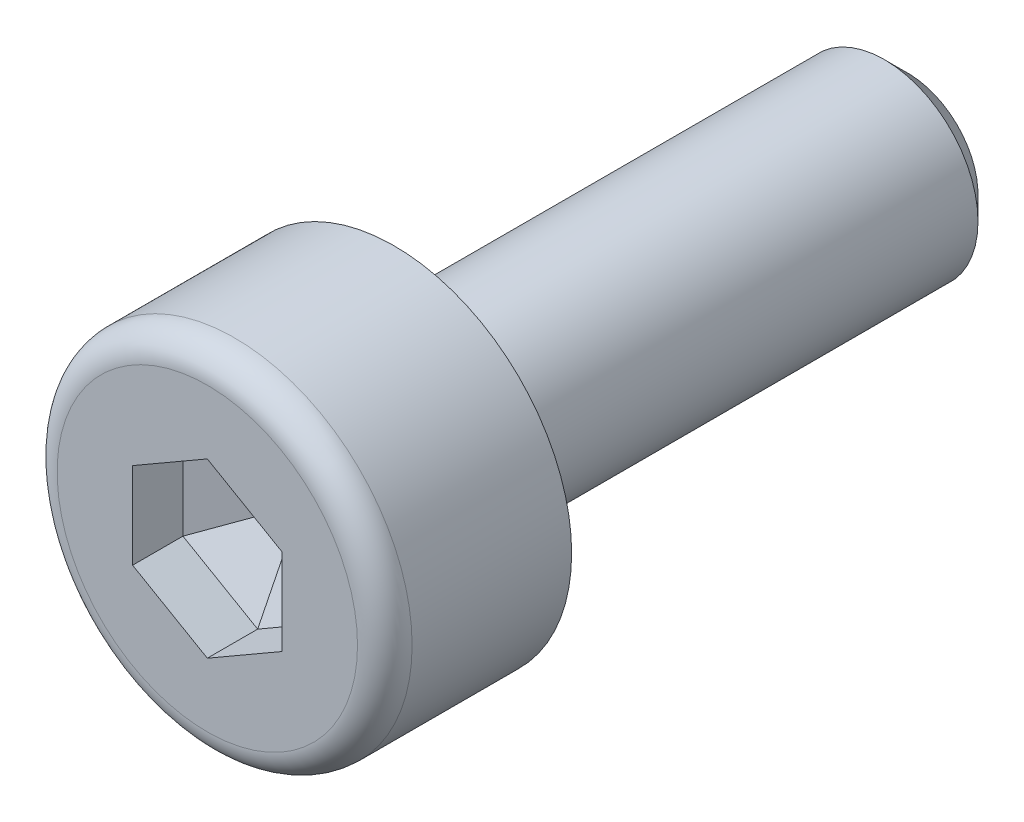
SolidWorks part; units mm, degrees
material "普通碳钢"
ref_plane "前视基准面" through (0, 0, 0) normal (0, 0, 1) x (1, 0, 0)
ref_plane "上视基准面" through (0, 0, 0) normal (0, 1, 0) x (1, 0, 0)
ref_plane "右视基准面" through (0, 0, 0) normal (1, 0, 0) x (0, 0, -1)
sketch "草图1" plane through (0, 0, 0) normal (0, 0, 1) x (1, 0, 0)
  circle A0 centre (0, 0) radius 1.9
  dimension "dk" = 3.8
extrude "凸台-拉伸1" add sketch "草图1" along normal blind 2
ref_axis "基准轴1" through (0, 0, 2) along (0, 0, -1)
sketch "草图2" plane through (0, 0, 2) normal (0, 0, 1) x (1, 0, 0)
  line L1 (0.8, 0.4619) -> (0, 0.9238)
  line L2 (0, 0.9238) -> (-0.8, 0.4619)
  line L3 (-0.8, 0.4619) -> (-0.8, -0.4619)
  line L4 (-0.8, -0.4619) -> (0, -0.9238)
  line L5 (0, -0.9238) -> (0.8, -0.4619)
  line L6 (0.8, -0.4619) -> (0.8, 0.4619)
  circle A0 centre (0, 0) radius 0.8 construction
  dimension "s" = 1.6
extrude "切除-拉伸1" cut sketch "草图2" against normal blind 1
sketch "草图3" plane through (0, 0, 0) normal (0, 0, -1) x (-1, 0, 0)
  circle A0 centre (0, 0) radius 1
  dimension "d" = 2
extrude "凸台-拉伸2" add sketch "草图3" along normal blind 5.5
cosmetic thread "装饰螺纹线1" parameters "b"=4.9, "D2"=1.221
chamfer "倒角1" distance 0.25 angle 45 1 edges at (-1, 0, -5.5)
fillet "圆角1" radius 0.2923 1 edges at (1.9, 0, 2)
chamfer "倒角2" distance 0.4611 angle 60 6 edges at (-0.8, 0, 1) (-0.4, 0.6928, 1) (0.4, 0.6928, 1) (0.8, 0, 1) (-0.4, -0.6928, 1) (0.4, -0.6928, 1) first distance on face at (-0.8, 0, 1.5) first distance on face at (-0.4, 0.6928, 1.5) first distance on face at (0.4, 0.6928, 1.5) first distance on face at (0.8, 0, 1.5) first distance on face at (-0.4, -0.6928, 1.5) first distance on face at (0.4, -0.6928, 1.5)
fillet "圆角2" radius 0.1 1 edges at (1, 0, 0)
ref_plane "基准面1" through (0, 0, 0) normal (0, 0, -1) x (-1, 0, 0)
equation "\"D1@倒角2\" = \"s@草图2\" / 3.47"
equation "\"D1@圆角1\"= \"dk@草图1\" / 13"
equation "\"D1@倒角1\"= \"d@草图3\" / 8"
equation "\"D1@圆角2\"= \"d@草图3\" / \"d@草图3\" * 0.1"
